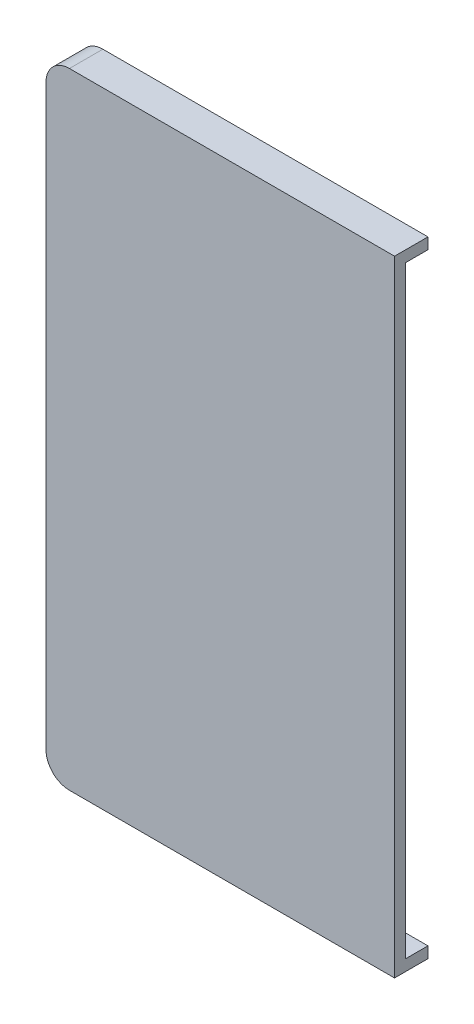
SolidWorks part; units mm, degrees
ref_plane "Front Plane" through (0, 0, 0) normal (0, 0, 1) x (1, 0, 0)
ref_plane "Top Plane" through (0, 0, 0) normal (0, 1, 0) x (1, 0, 0)
ref_plane "Right Plane" through (0, 0, 0) normal (1, 0, 0) x (0, 0, -1)
sketch "Sketch1" plane through (0, 0, 0) normal (0, 0, 1) x (1, 0, 0)
  line L4 (657.3112, -1230.231) -> (657.3112, -1334.011)
  line L5 (661.5112, -1338.211) -> (719.8512, -1338.211)
  line L7 (719.8512, -1226.031) -> (661.5112, -1226.031)
  line L8 (659.3112, -1230.231) -> (659.3112, -1334.011)
  line L9 (661.5112, -1336.211) -> (769.8512, -1336.211)
  line L10 (772.0512, -1334.011) -> (772.0512, -1230.231)
  line L11 (769.8512, -1228.031) -> (661.5112, -1228.031)
  line L12 (659.3112, -1230.231) -> (659.3112, -1334.011)
  line L13 (661.5112, -1336.211) -> (719.8512, -1336.211)
  line L15 (719.8512, -1228.031) -> (661.5112, -1228.031)
  line L16 (719.8512, -1327.661) -> (719.8512, -1261.621) construction
  line L17 (719.8512, -1327.661) -> (719.8512, -1261.621)
  line L18 (719.8512, -1261.621) -> (719.8512, -1226.031)
  line L19 (719.8512, -1327.661) -> (719.8512, -1338.211)
  line L20 (769.8512, -1226.031) -> (661.5112, -1226.031) construction
  line L21 (769.8512, -1228.031) -> (661.5112, -1228.031) construction
  line L22 (661.5112, -1336.211) -> (769.8512, -1336.211) construction
  line L23 (661.5112, -1338.211) -> (769.8512, -1338.211) construction
  line L24 (772.0512, -1334.011) -> (772.0512, -1230.231) construction
  line L25 (774.0512, -1334.011) -> (774.0512, -1230.231) construction
  arc A4 (657.3112, -1334.011) -> (661.5112, -1338.211) centre (661.5112, -1334.011) ccw
  arc A7 (661.5112, -1226.031) -> (657.3112, -1230.231) centre (661.5112, -1230.231) ccw
  arc A8 (659.3112, -1334.011) -> (661.5112, -1336.211) centre (661.5112, -1334.011) ccw
  arc A9 (769.8512, -1336.211) -> (772.0512, -1334.011) centre (769.8512, -1334.011) ccw
  arc A10 (772.0512, -1230.231) -> (769.8512, -1228.031) centre (769.8512, -1230.231) ccw
  arc A11 (661.5112, -1228.031) -> (659.3112, -1230.231) centre (661.5112, -1230.231) ccw
  arc A12 (659.3112, -1334.011) -> (661.5112, -1336.211) centre (661.5112, -1334.011) ccw
  arc A15 (661.5112, -1228.031) -> (659.3112, -1230.231) centre (661.5112, -1230.231) ccw
  arc A20 (774.0512, -1230.231) -> (769.8512, -1226.031) centre (769.8512, -1230.231) ccw construction
  arc A21 (772.0512, -1230.231) -> (769.8512, -1228.031) centre (769.8512, -1230.231) ccw construction
  arc A22 (769.8512, -1338.211) -> (774.0512, -1334.011) centre (769.8512, -1334.011) ccw construction
  arc A23 (769.8512, -1336.211) -> (772.0512, -1334.011) centre (769.8512, -1334.011) ccw construction
extrude "Boss-Extrude1" add sketch "Sketch1" along normal blind 2 contours A15 L15 L18 L7 A7 L4 A4 L5 L19 L13 A12 L12 | L15 A15 L12 A12 L13 L19 L17 L18 region at (659.4496, -1228.1693, 0) region at (689.5907, -1282.121, 0)
extrude "Boss-Extrude2" add sketch "Sketch1<3>" against normal blind 4 contours A15 L15 L18 L7 A7 L4 A4 L5 L19 L13 A12 L12 region at (659.4496, -1228.1693, 0)
sketch "Sketch1<3>" plane through (0, 0, 0) normal (0, 0, 1) x (1, 0, 0) same geometry as "Sketch1"
equation "\"C\"=0.2"
equation "\"D1@Sketch1\"=\"C\""
equation "\"T\"=2"
equation "\"D2@Sketch1\"=\"T\""
equation "\"D1@Boss-Extrude1\"=\"T\""
equation "\"HANG\"=4"
equation "\"D2@Boss-Extrude1\"=\"HANG\""
equation "\"D1@Boss-Extrude2\"=\"HANG\""
equation "\"OFF1\"=55"
equation "\"OFF2\"=25"
equation "\"D2@Sketch2\"=\"OFF2\""
equation "\"HOLED\"= 10"
equation "\"D3@Sketch2\"=\"HOLED\""
equation "\"D1@Sketch2\"=\"OFF1\""
